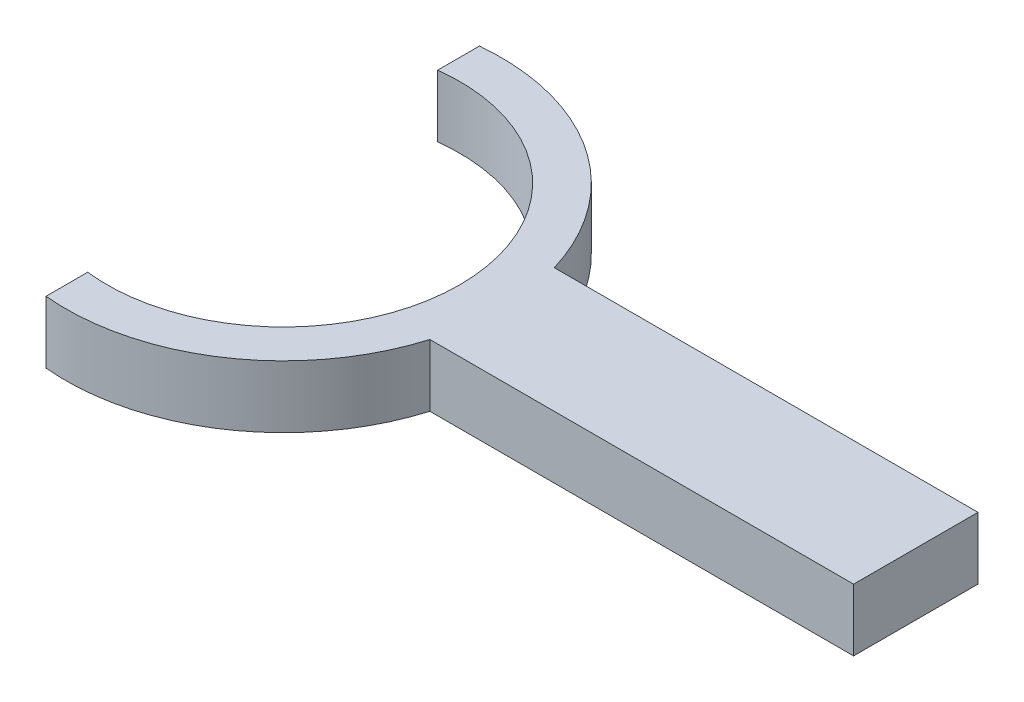
SolidWorks part; units mm, degrees
ref_plane "前视基准面" through (0, 0, 0) normal (0, 0, 1) x (1, 0, 0)
ref_plane "上视基准面" through (0, 0, 0) normal (0, 1, 0) x (1, 0, 0)
ref_plane "右视基准面" through (0, 0, 0) normal (1, 0, 0) x (0, 0, -1)
other "Configuration Table"
sketch "草图1" plane through (0, 0, 0) normal (0, 1, 0) x (1, 0, 0)
  circle A0 centre (0, 0) radius 4.25
  circle A1 centre (0, 0) radius 5.25
  dimension "D1" = 8.5
  dimension "D2" = 1
extrude "凸台-拉伸1" add sketch "草图1" along normal blind 1.5
ref_plane "基准面1" through (5.25, 0, 0) normal (1, 0, 0) x (0, 0, -1)
sketch "草图2" plane through (5.25, 0, 0) normal (1, 0, 0) x (0, 0, -1)
  line L0 (5.25, 1.5) -> (-5.25, 1.5) construction
  line L1 (-1.5, 1.5) -> (1.5, 1.5)
  line L2 (-1.5, 1.5) -> (-1.5, 0)
  line L3 (-1.5, 0) -> (1.5, 0)
  line L4 (1.5, 1.5) -> (1.5, 0)
  line L5 (0, 0) -> (0, 0.8122) construction
  point P8 (0, 0)
  dimension "D1" = 3
extrude "凸台-拉伸2" add sketch "草图2" along normal blind 10 and the other way blind 0.5
sketch "草图3" plane through (0, 1.5, 0) normal (0, 1, 0) x (1, 0, 0)
  line L0 (15.25, 1.5) -> (15.25, -1.5) construction
  line L1 (-6.962, 5.9347) -> (-0.5, 5.9347)
  line L2 (-6.962, 5.9347) -> (-6.962, -6.1689)
  line L3 (-6.962, -6.1689) -> (-0.5, -6.1689)
  line L4 (-0.5, 5.9347) -> (-0.5, -6.1689)
  line L5 (15.25, 1.5) -> (15.25, -1.5) construction
  dimension "D1" = 0.5
extrude "切除-拉伸1" cut sketch "草图3" against normal up to next
